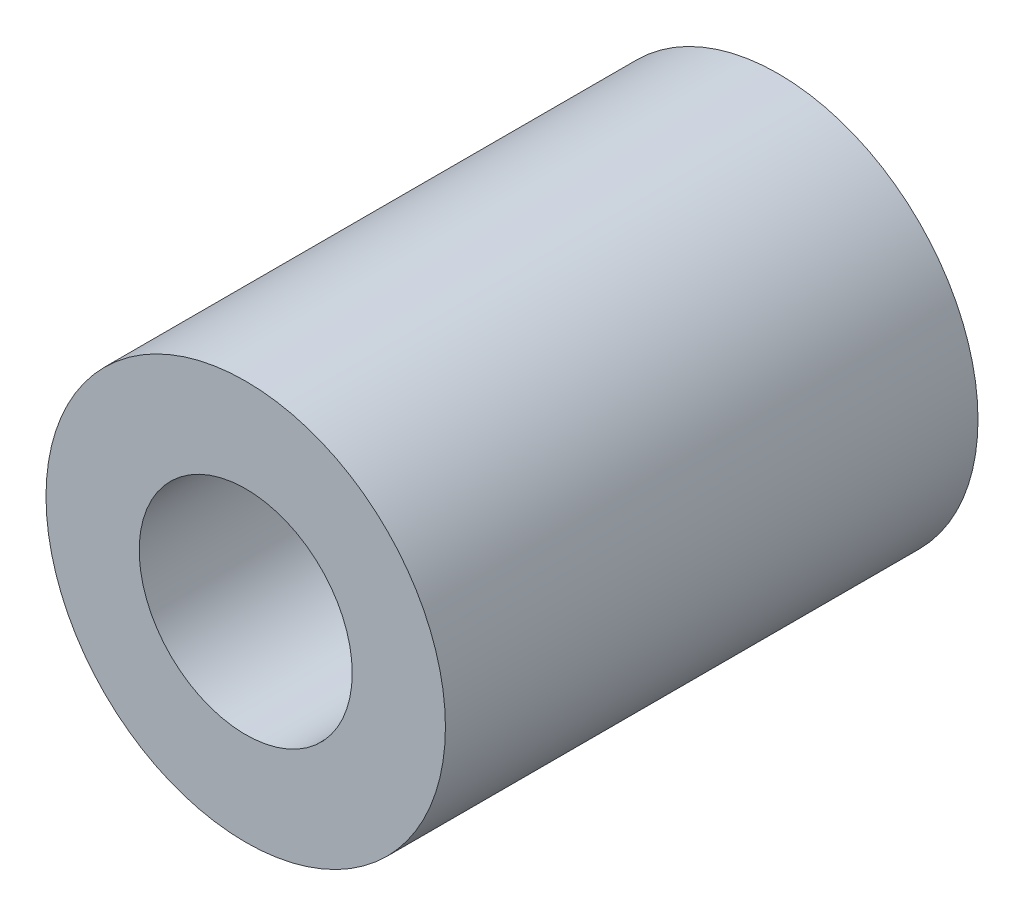
SolidWorks part; units mm, degrees
material "ABS"
ref_plane "Front Plane" through (0, 0, 0) normal (0, 0, 1) x (1, 0, 0)
ref_plane "Top Plane" through (0, 0, 0) normal (0, 1, 0) x (1, 0, 0)
ref_plane "Right Plane" through (0, 0, 0) normal (1, 0, 0) x (0, 0, -1)
sketch "Sketch1" plane through (0, 0, 0) normal (0, 0, 1) x (1, 0, 0)
  circle A0 centre (0, 0) radius 4
  circle A1 centre (0, 0) radius 7.5
extrude "Boss-Extrude2" add sketch "Sketch1" along normal blind 20
